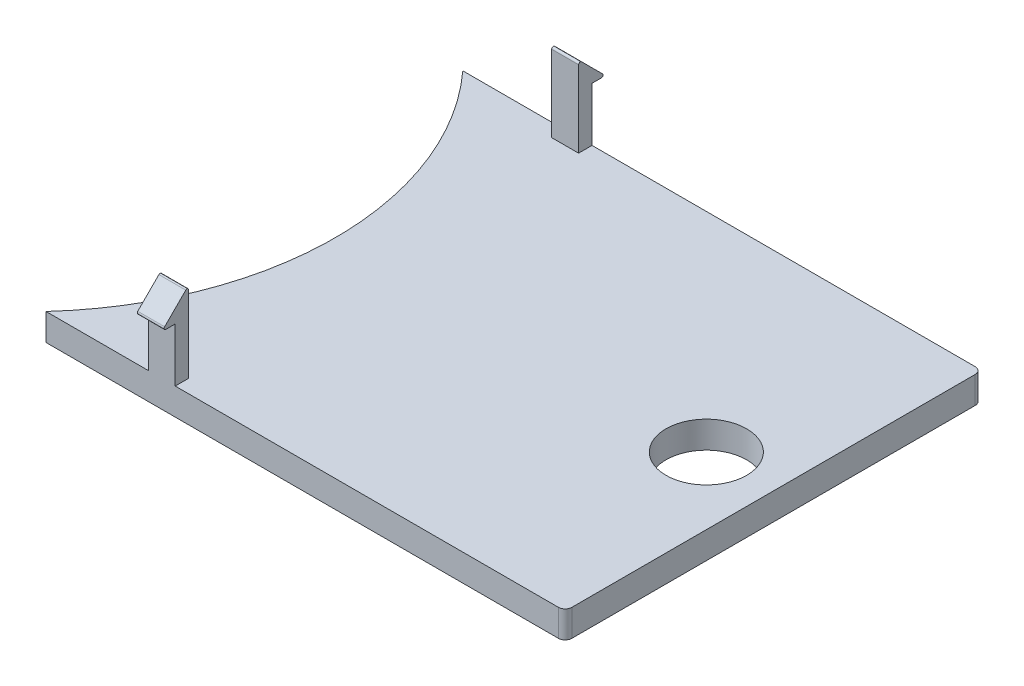
SolidWorks part; units mm, degrees
ref_plane "前视基准面" through (0, 0, 0) normal (0, 0, 1) x (1, 0, 0)
ref_plane "上视基准面" through (0, 0, 0) normal (0, 1, 0) x (1, 0, 0)
ref_plane "右视基准面" through (0, 0, 0) normal (1, 0, 0) x (0, 0, -1)
other "Configuration Table"
sketch "草图1" plane through (0, 0, 0) normal (0, 1, 0) x (1, 0, 0)
  line L0 (37.61, 31) -> (-38.61, 31)
  line L1 (-38.61, 31) -> (-38.61, -31)
  line L2 (-38.61, -31) -> (37.61, -31)
  line L3 (38.61, 30) -> (38.61, -30)
  line L5 (38.61, 0) -> (-38.61, 0) construction
  arc A0 (37.61, 31) -> (38.61, 30) centre (37.61, 30) cw
  arc A1 (37.61, -31) -> (38.61, -30) centre (37.61, -30) ccw
  circle A3 centre (-72.5953, 0) radius 46
  point P9 (0, 0)
  dimension "D1" = 1
  dimension "D2" = 1
  dimension "D6" = 92
  dimension "D3" = 77.22
  dimension "D4" = 62
extrude "凸台-拉伸1" add sketch "草图1" along normal blind 4 contours L5 L3 A0 L0 A3 | L3 L5 A3 L2 A1 region at (4.0307, 0, -15.9339) region at (4.0307, 0, 15.9339)
ref_plane "卡扣拉伸基准面" through (-21.39, 0, 0) normal (1, 0, 0) x (0, 0, -1)
sketch "草图3" plane through (-21.39, 0, 0) normal (1, 0, 0) x (0, 0, -1)
  line L0 (-31, 4) -> (-31, 12)
  line L1 (30, 4) -> (-30, 4) construction
  line L2 (-31, 12) -> (-33, 12)
  line L3 (-33, 12) -> (-29, 16)
  line L4 (-29, 16) -> (-29, 4)
  line L5 (-29, 4) -> (-31, 4)
  line L7 (-31, 4) -> (-31, 0) construction
  dimension "D1" = 2
  dimension "D2" = 8
  dimension "D3" = 2
  dimension "D4" = 4
extrude "卡扣-凸台-拉伸" add sketch "草图3" along normal blind 2 and the other way blind 2
fillet "圆角1" radius 0.25 2 edges at (-21.39, 16, 29) (-21.39, 12, 33)
mirror "镜向1" about plane through (0, 0, 0) normal (0, 0, 1) of "圆角1", "卡扣-凸台-拉伸"
sketch "草图4" plane through (0, 0, 0) normal (0, -1, 0) x (1, 0, 0)
  line L0 (0, 0) -> (38.61, 0) construction
  line L1 (38.61, -30) -> (38.61, 30) construction
  circle A0 centre (28.61, 0) radius 6
  dimension "D1" = 12
  dimension "D2" = 10
extrude "切除-拉伸2" cut sketch "草图4" against normal through all
